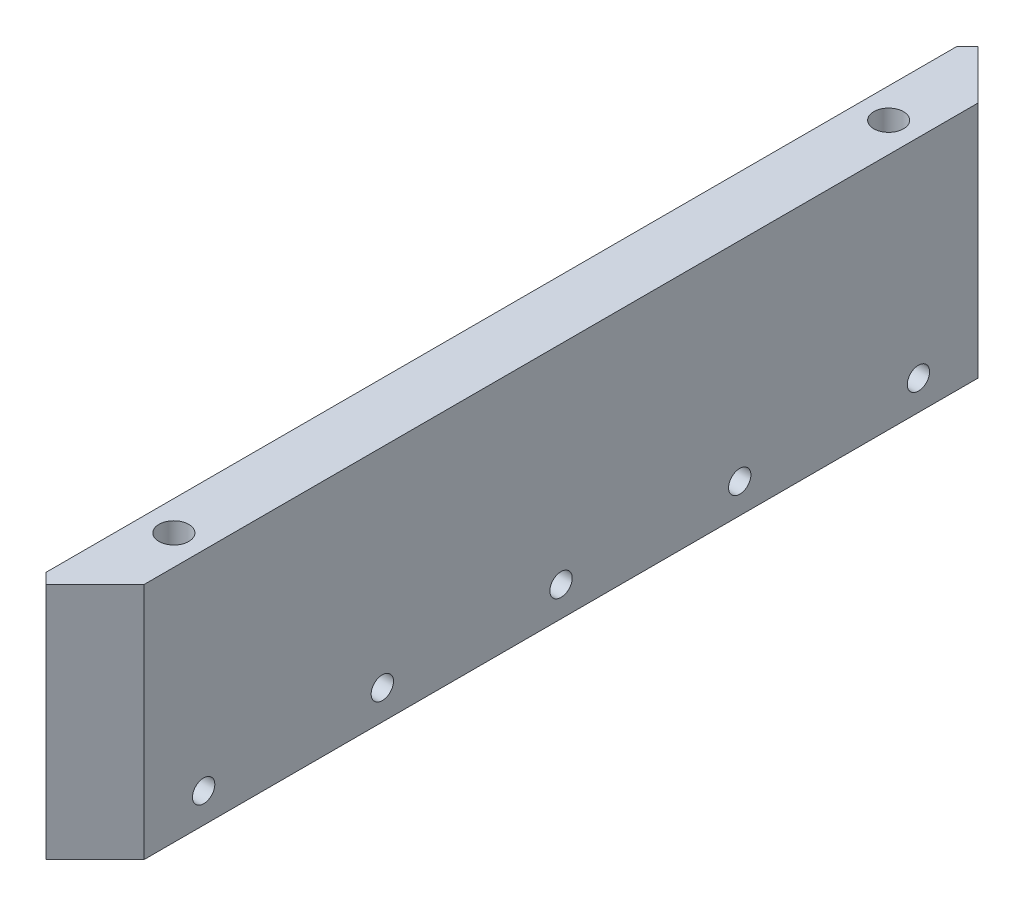
SolidWorks part; units mm, degrees
material "Mahogany"
ref_plane "Front Plane" through (0, 0, 0) normal (0, 0, 1) x (1, 0, 0)
ref_plane "Top Plane" through (0, 0, 0) normal (0, 1, 0) x (1, 0, 0)
ref_plane "Right Plane" through (0, 0, 0) normal (1, 0, 0) x (0, 0, -1)
sketch "Sketch1" plane through (0, 0, 0) normal (1, 0, 0) x (0, 0, -1)
  line L1 (-101.6, 25.4) -> (101.6, 25.4)
  line L2 (-101.6, 25.4) -> (-101.6, -25.4)
  line L3 (-101.6, -25.4) -> (101.6, -25.4)
  line L4 (101.6, 25.4) -> (101.6, -25.4)
  line L5 (-101.6, 25.4) -> (101.6, -25.4) construction
  line L6 (-101.6, -25.4) -> (101.6, 25.4) construction
  point P0 (0, 0)
  dimension "D1" = 203.2
  dimension "D2" = 50.8
extrude "Boss-Extrude1" add sketch "Sketch1" along normal blind 12.7
sketch "Sketch2" plane through (0, 25.4, 0) normal (0, 1, 0) x (1, 0, 0)
  line L0 (0, 101.6) -> (12.7, 88.9)
  line L1 (12.7, 101.6) -> (12.7, -101.6) construction
  line L2 (12.7, 88.9) -> (12.7, 101.6)
  line L3 (12.7, 101.6) -> (0, 101.6)
  line L4 (0, -101.6) -> (12.7, -88.9)
  line L5 (12.7, -88.9) -> (12.7, -101.6)
  line L6 (12.7, -101.6) -> (0, -101.6)
extrude "Cut-Extrude1" cut sketch "Sketch2" against normal through all
sketch "Sketch3" plane through (0, 25.4, 0) normal (0, 1, 0) x (1, 0, 0)
  line L0 (0, 97.1099) -> (2.2451, 99.3549)
  line L1 (0, 101.6) -> (0, -101.6) construction
  line L2 (0, 101.6) -> (12.7, 88.9) construction
  line L3 (2.2451, 99.3549) -> (0, 101.6)
  line L4 (0, 101.6) -> (0, 97.1099)
  line L5 (0, -97.1099) -> (2.2451, -99.3549)
  line L6 (12.7, -88.9) -> (0, -101.6) construction
  line L7 (2.2451, -99.3549) -> (0, -101.6)
  line L8 (0, -101.6) -> (0, -97.1099)
  dimension "D1" = 3.175
extrude "Cut-Extrude2" cut sketch "Sketch3" against normal through all
sketch "Sketch4" plane through (0, 0, 0) normal (-1, 0, 0) x (0, 0, 1)
  line L0 (97.1099, -25.4) -> (-97.1099, -25.4) construction
  line L1 (-101.6, -995.2026) -> (-101.6, 49004.7974) construction
  circle A0 centre (-76.2, -19.05) radius 2.3813
  dimension "D1" = 4.7625
  dimension "D2" = 6.35
  dimension "D3" = 101.6
  dimension "D4" = 25.4
extrude "Cut-Extrude3" cut sketch "Sketch4" against normal through all
pattern_linear "LPattern1" count 5 spacing 38.1 along (0, 0, 1) of "Cut-Extrude3"
sketch "Sketch5" plane through (0, 25.4, 0) normal (0, 1, 0) x (1, 0, 0)
  line L0 (0, 97.1099) -> (0, -97.1099) construction
  line L1 (6.35, 76.2) -> (0, 0) construction
  line L2 (0, 0) -> (6.35, -76.2) construction
  circle A0 centre (6.35, 76.2) radius 3.175
  circle A1 centre (6.35, -76.2) radius 3.175
  dimension "D2" = 6.35
  dimension "D1" = 6.35
  dimension "D3" = 152.4
extrude "Cut-Extrude4" cut sketch "Sketch5" against normal blind 12.7
